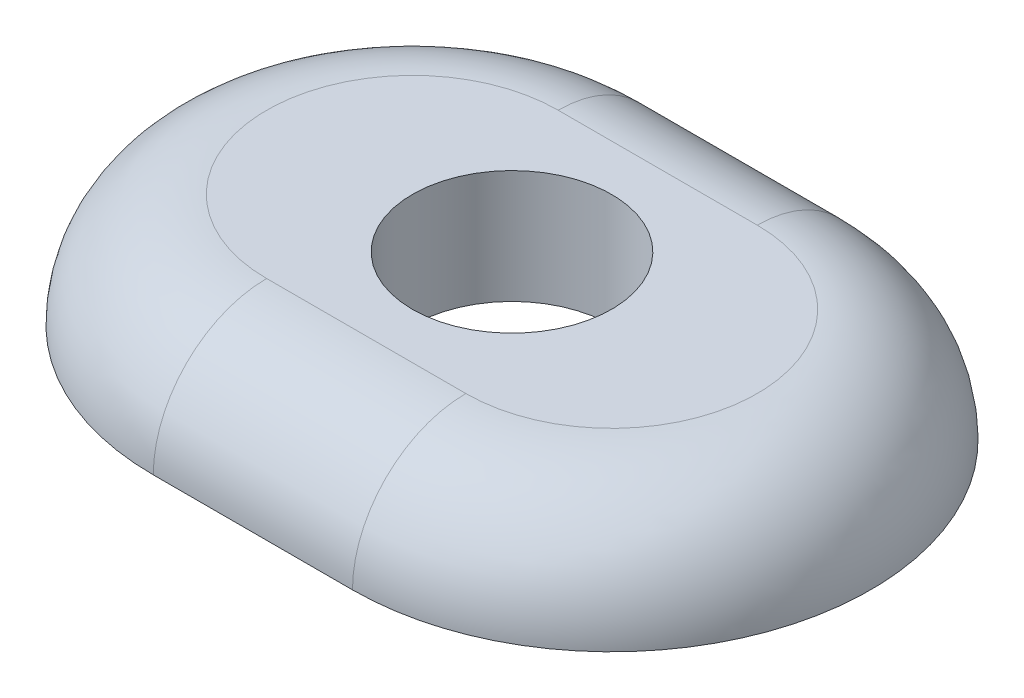
SolidWorks part; units mm, degrees
ref_plane "Front Plane" through (0, 0, 0) normal (0, 0, 1) x (1, 0, 0)
ref_plane "Top Plane" through (0, 0, 0) normal (0, 1, 0) x (1, 0, 0)
ref_plane "Right Plane" through (0, 0, 0) normal (1, 0, 0) x (0, 0, -1)
sketch "Sketch2" plane through (0, 0, 0) normal (0, 1, 0) x (1, 0, 0)
  line L0 (-6.15, 16) -> (6.15, 16)
  line L1 (-6.15, -16) -> (6.15, -16)
  circle A0 centre (0, 0) radius 6.15
  arc A2 (-6.15, 16) -> (-6.15, -16) centre (-6.15, 0) ccw
  arc A3 (6.15, -16) -> (6.15, 16) centre (6.15, 0) ccw
  dimension "D1" = 12.3
  dimension "D3" = 32
  dimension "D4" = 32
extrude "Boss-Extrude1" add sketch "Sketch2" along normal blind 7
fillet "Fillet2" radius 7 4 edges at (-22.15, 7, 0) (0, 7, -16) (22.15, 7, 0) (0, 7, 16)
